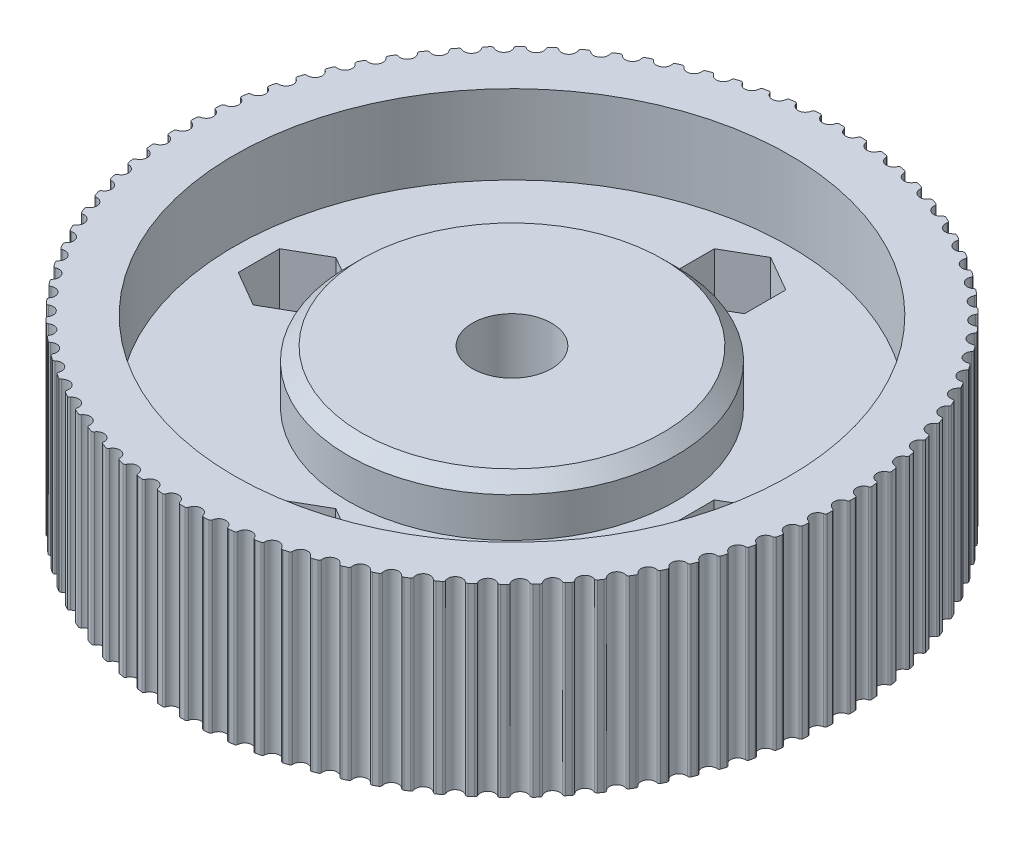
SolidWorks part; units mm, degrees
ref_plane "Front Plane" through (0, 0, 0) normal (0, 0, 1) x (1, 0, 0)
ref_plane "Top Plane" through (0, 0, 0) normal (0, 1, 0) x (1, 0, 0)
ref_plane "Right Plane" through (0, 0, 0) normal (1, 0, 0) x (0, 0, -1)
sketch "Sketch1" plane through (0, 0, 0) normal (0, 1, 0) x (1, 0, 0)
  circle A0 centre (0, 0) radius 25
  circle A1 centre (0, 0) radius 6.85
  dimension "D1" = 50
  dimension "D2" = 13.7
extrude "Boss-Extrude1" add sketch "Sketch1" along normal blind 14
sketch "Sketch2" plane through (0, 14, 0) normal (0, 1, 0) x (1, 0, 0)
  circle A0 centre (0, 0) radius 21.075
  circle A1 centre (0, 0) radius 12.425
  dimension "D1" = 42.15
  dimension "D2" = 24.85
extrude "Cut-Extrude1" cut sketch "Sketch2" against normal blind 6
sketch "Sketch5" plane through (0, 14, 0) normal (0, 1, 0) x (1, 0, 0)
  line L0 (0, 0) -> (25, 0) construction
  circle A0 centre (0, 0) radius 25 construction
  circle A1 centre (25, 0) radius 0.55
  dimension "D1" = 1.1
extrude "Cut-Extrude3" cut sketch "Sketch5" against normal up to surface (14 mm away) up to face at (0, 0, 25)
fillet "Fillet1" radius 0.16 2 edges at (24.994, 7, 0.55) (24.994, 7, -0.55)
pattern_circular "CirPattern1" count 90 over 360 about axis through (0, 14, 0) along (0, -1, 0) of "Cut-Extrude3", "Fillet1" reverse direction yes
sketch "Sketch9" plane through (0, 14, 0) normal (0, 1, 0) x (1, 0, 0)
  circle A0 centre (0, 0) radius 6.85
  circle A1 centre (0, 0) radius 12.45
  dimension "D1" = 24.9
extrude "Cut-Extrude4" cut sketch "Sketch9" against normal blind 2
sketch "Sketch10" plane through (0, 8, 0) normal (0, 1, 0) x (1, 0, 0)
  circle A0 centre (0, 0) radius 16.5 construction
  circle A3 centre (16.5, 0) radius 1.5
  circle A4 centre (0, -16.5) radius 1.5
  circle A5 centre (-16.5, 0) radius 1.5
  circle A6 centre (0, 16.5) radius 1.5
  point P14 (0, 0)
  dimension "D1" = 33
  dimension "D2" = 3
  dimension "D3" = 4
extrude "Cut-Extrude5" cut sketch "Sketch10" against normal up to surface (8 mm away) up to face at (0, 0, 0)
sketch "Sketch11" plane through (0, 8, 0) normal (0, 1, 0) x (1, 0, 0)
  line L24 (16.5, 0) -> (12.425, 0) construction
  line L27 (16.511, -3.125) -> (19.2118, -1.553)
  line L28 (19.2118, -1.553) -> (19.2008, 1.572)
  line L29 (19.2008, 1.572) -> (16.489, 3.125)
  line L30 (16.489, 3.125) -> (13.7882, 1.553)
  line L31 (13.7882, 1.553) -> (13.7992, -1.572)
  line L32 (13.7992, -1.572) -> (16.511, -3.125)
  line L34 (-13.7992, -1.572) -> (-16.511, -3.125)
  line L35 (-13.7882, 1.553) -> (-13.7992, -1.572)
  line L36 (-16.489, 3.125) -> (-13.7882, 1.553)
  line L37 (-19.2008, 1.572) -> (-16.489, 3.125)
  line L38 (-19.2118, -1.553) -> (-19.2008, 1.572)
  line L39 (-16.511, -3.125) -> (-19.2118, -1.553)
  line L40 (-16.5, 0) -> (-12.45, 0) construction
  line L42 (0, -12.4) -> (0, -16.5) construction
  line L43 (0, 13.375) -> (2.7063, 14.9375)
  line L44 (2.7063, 14.9375) -> (2.7063, 18.0625)
  line L45 (2.7063, 18.0625) -> (0, 19.625)
  line L46 (0, 19.625) -> (-2.7063, 18.0625)
  line L47 (-2.7063, 18.0625) -> (-2.7063, 14.9375)
  line L48 (-2.7063, 14.9375) -> (0, 13.375)
  line L49 (-2.7063, -14.9375) -> (0, -13.375)
  line L50 (-2.7063, -18.0625) -> (-2.7063, -14.9375)
  line L51 (0, -19.625) -> (-2.7063, -18.0625)
  line L52 (2.7063, -18.0625) -> (0, -19.625)
  line L53 (2.7063, -14.9375) -> (2.7063, -18.0625)
  line L54 (0, -13.375) -> (2.7063, -14.9375)
  circle A0 centre (0, 0) radius 12.425 construction
  circle A2 centre (16.5, 0) radius 2.7063 construction
  circle A3 centre (0, 16.5) radius 2.7063 construction
  dimension "D1" = 6.25
extrude "Cut-Extrude6" cut sketch "Sketch11" against normal blind 4
sketch "Sketch12" plane through (0, 12, 0) normal (0, 1, 0) x (1, 0, 0)
  circle A0 centre (0, 0) radius 6.85
  circle A1 centre (0, 0) radius 3
  dimension "D1" = 6
extrude "Boss-Extrude2" add sketch "Sketch12" against normal blind 5
sketch "Sketch14" plane through (0, 12, 0) normal (0, 1, 0) x (1, 0, 0)
  circle A0 centre (0, 0) radius 25
chamfer "Chamfer2" distance 1 angle 45 1 edges at (0, 12, 12.425)
